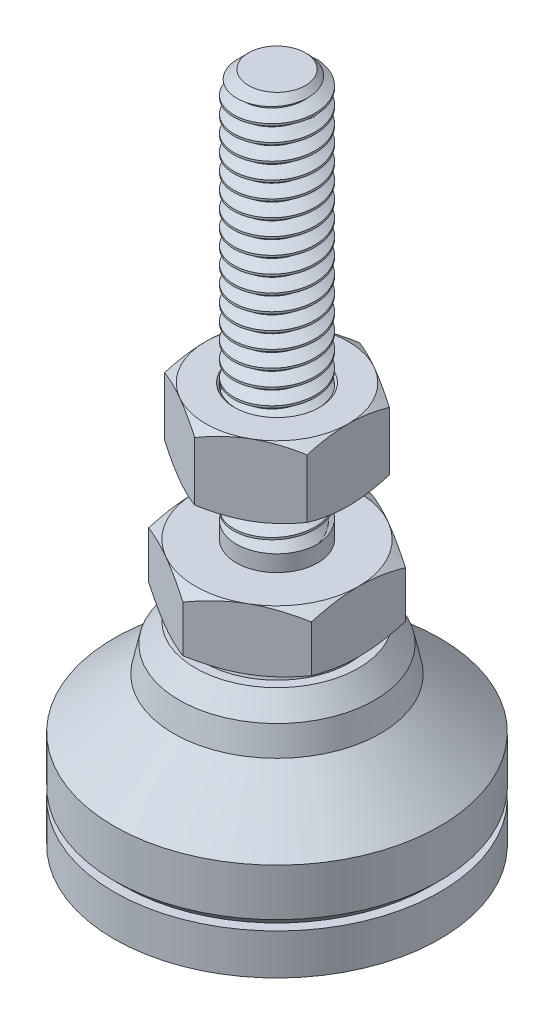
SolidWorks part; units mm, degrees
ref_plane "Front Plane" through (0, 0, 0) normal (0, 0, 1) x (1, 0, 0)
ref_plane "Top Plane" through (0, 0, 0) normal (0, 1, 0) x (1, 0, 0)
ref_plane "Right Plane" through (0, 0, 0) normal (1, 0, 0) x (0, 0, -1)
sketch "Sketch1" plane through (0, 0, 0) normal (0, 0, 1) x (1, 0, 0)
  line L0 (0, 0) -> (0, 52.3875) construction
  line L1 (-12.7, 0) -> (12.7, 0) construction
  line L2 (-3.175, 52.3875) -> (3.175, 52.3875) construction
  line L3 (-6.35, 15.875) -> (6.35, 15.875) construction
  point P7 (0, 20.6375)
  point P10 (0, 15.875)
  point P11 (-6.35, 20.6375)
  point P12 (0, 3.175)
  dimension "D1" = 3.175
sketch "Sketch2" plane through (0, 0, 0) normal (0, 0, 1) x (1, 0, 0)
  line L0 (0, 3.175) -> (0, 7.747)
  line L1 (-5.842, 15.875) -> (-6.35, 15.875) construction
  line L2 (-7.62, 13.589) -> (-6.35, 15.113)
  line L3 (-6.35, 15.113) -> (-5.6397, 15.113)
  line L4 (-7.62, 13.589) -> (-8.0645, 11.557)
  line L5 (-8.0645, 11.557) -> (-12.7, 7.62)
  line L6 (-12.7, 7.62) -> (-12.7, 3.937)
  line L7 (-11.938, 3.175) -> (0, 3.175)
  line L8 (-7.62, 13.589) -> (0, 13.589) construction
  line L9 (-5.842, 13.589) -> (-5.842, 15.875) construction
  line L10 (-12.7, 3.937) -> (-11.938, 3.175)
  line L11 (-11.938, 3.175) -> (-12.7, 3.175) construction
  line L12 (-12.7, 3.175) -> (-12.7, 3.937) construction
  line L13 (0, 15.875) -> (0, 52.3875) construction
  line L14 (-3.175, 52.3875) -> (3.175, 52.3875) construction
  line L15 (-6.35, 15.875) -> (6.35, 15.875) construction
  circle A0 centre (0, 13.589) radius 5.842 construction
  arc A2 (-5.6397, 15.113) -> (0, 7.747) centre (0, 13.589) ccw
  dimension "D1" = 16.129
  dimension "D2" = 15.24
  dimension "D3" = 12.7
  dimension "D4" = 0.508
  dimension "H3" = 2.032
  dimension "C1" = 0.762
  dimension "H4" = 1.524
  dimension "H2" = 3.937
  dimension "H1" = 4.445
revolve "Revolve1" add sketch "Sketch2" angle 360 about L0
sketch "Sketch12" plane through (0, 0, 0) normal (0, 0, 1) x (1, 0, 0)
  line L0 (0, 15.875) -> (-5.3762, 15.875)
  line L1 (0, 15.875) -> (0, 7.747)
  arc A0 (-5.3762, 15.875) -> (0, 7.747) centre (0, 13.589) ccw
  circle A1 centre (0, 13.589) radius 5.842 construction
revolve "Revolve2" add sketch "Sketch12" angle 360 about L1
sketch "Sketch4" plane through (0, 15.875, 0) normal (0, 1, 0) x (1, 0, 0)
  line L1 (0, 7.3323) -> (-6.35, 3.6662)
  line L2 (-6.35, 3.6662) -> (-6.35, -3.6662)
  line L3 (-6.35, -3.6662) -> (0, -7.3323)
  line L4 (0, -7.3323) -> (6.35, -3.6662)
  line L5 (6.35, -3.6662) -> (6.35, 3.6662)
  line L6 (6.35, 3.6662) -> (0, 7.3323)
  circle A0 centre (0, 0) radius 6.35 construction
extrude "Boss-Extrude1" add sketch "Sketch4" along normal up to vertex (4.7625 mm away) up to point (0, 20.6375, 0)
sketch "Sketch5" plane through (0, 0, 0) normal (1, 0, 0) x (0, 0, -1)
  line L0 (-8.3147, 20.6375) -> (-8.3147, 15.875)
  line L1 (-8.3147, 15.875) -> (-6.35, 15.875)
  line L2 (-6.35, 15.875) -> (-7.3323, 16.4422)
  line L3 (-7.3323, 16.4422) -> (-7.3323, 20.0703)
  line L4 (-7.3323, 20.0703) -> (-6.35, 20.6375)
  line L5 (-6.35, 20.6375) -> (-8.3147, 20.6375)
  line L9 (-7.3323, 20.6375) -> (-7.3323, 15.875) construction
  dimension "D1" = 30
revolve "Cut-Revolve2" cut sketch "Sketch5" angle 360 about L0
sketch "Sketch6" plane through (0, 20.6375, 0) normal (0, 1, 0) x (1, 0, 0)
  circle A0 centre (0, 0) radius 3.175
extrude "Boss-Extrude2" add sketch "Sketch6" along normal up to vertex (31.75 mm away) separate body up to point (0, 52.3875, 0)
sketch "Sketch7" plane through (0, 52.3875, 0) normal (0, 1, 0) x (1, 0, 0)
  circle A1 centre (0, 0) radius 3.175
  circle A2 centre (0, 0) radius 3.175
  point P0 (3.175, 0)
  dimension "D1" = 0
curve "Helix/Spiral1" pitch 1.27 height 33.02 turns 26 parameters "Pitch"=1.27
sketch "Sketch8" plane through (0, 0, 0) normal (0, 0, 1) x (1, 0, 0)
  line L0 (3.3125, 53.5781) -> (3.3125, 52.3081) construction
  line L1 (3.3125, 52.3081) -> (2.2126, 52.9431) construction
  line L2 (2.2126, 52.9431) -> (3.3125, 53.5781) construction
  line L3 (2.3501, 53.0225) -> (2.3501, 52.8638) construction
  line L4 (3.175, 53.4988) -> (3.175, 52.3875) construction
  line L5 (2.2126, 52.9431) -> (2.3501, 52.9431) construction
  line L6 (3.175, 52.9431) -> (3.3125, 52.9431) construction
  line L7 (3.2437, 53.5384) -> (2.3501, 53.0225)
  line L8 (2.3501, 53.0225) -> (2.3501, 52.8638)
  line L9 (2.3501, 52.8638) -> (3.2437, 52.3478)
  line L10 (3.2437, 52.3478) -> (3.2437, 53.5384)
  line L11 (3.3125, 52.3081) -> (3.175, 52.3081) construction
  line L12 (3.175, 52.3081) -> (3.175, 36.4331) construction
  line L20 (3.175, 20.6375) -> (3.175, 52.3875) construction
  point P11 (3.2437, 52.9431)
  dimension "D1" = 1.27
  dimension "D2" = 0.1588
  dimension "D3" = 15.875
sketch "Sketch9" plane through (0, 52.3875, 0) normal (0, 1, 0) x (1, 0, 0)
  circle A0 centre (0, 0) radius 2.2126
sweep "Cut-Sweep1" cut profiles "Sketch8" path "Helix/Spiral1" align with end faces yes
extrude "Cut-Extrude1" cut sketch "Sketch9" against normal up to vertex (31.75 mm away) draft 45 flip side to cut up to point (0, 20.6375, 0)
combine bodies "Combine1" operation type add bodies to combine 107 104
ref_plane "Plane1" through (0, 31.2208, 0) normal (0, 1, 0) x (-1, 0, 0)
sketch "Sketch10" plane through (0, 31.2208, 0) normal (0, 1, 0) x (-1, 0, 0)
  line L1 (0, 6.4158) -> (-5.5563, 3.2079)
  line L2 (-5.5563, 3.2079) -> (-5.5562, -3.2079)
  line L3 (-5.5562, -3.2079) -> (0, -6.4158)
  line L4 (0, -6.4158) -> (5.5562, -3.2079)
  line L5 (5.5562, -3.2079) -> (5.5562, 3.2079)
  line L6 (5.5562, 3.2079) -> (0, 6.4158)
  circle A0 centre (0, 0) radius 5.5562 construction
  circle A1 centre (0, 0) radius 3.175
  dimension "Nut Width" = 11.1125
extrude "Boss-Extrude3" add sketch "Sketch10" against normal blind 5.5562 separate body
sketch "Sketch11" plane through (0, 0, 0) normal (1, 0, 0) x (0, 0, -1)
  line L0 (-7.2754, 25.6646) -> (-7.2754, 31.2208)
  line L1 (-7.2754, 31.2208) -> (-5.5562, 31.2208)
  line L2 (-5.5562, 31.2208) -> (-6.4158, 30.7246)
  line L3 (-6.4158, 30.7246) -> (-6.4158, 26.1608)
  line L4 (-6.4158, 26.1608) -> (-5.5562, 25.6646)
  line L5 (-5.5562, 25.6646) -> (-7.2754, 25.6646)
  line L6 (-6.4158, 25.6646) -> (-6.4158, 31.2208) construction
  line L11 (0, 25.6646) -> (0, 31.2208)
  line L12 (0, 31.2208) -> (3.3338, 31.2208)
  line L13 (3.3338, 31.2208) -> (3.175, 31.0621)
  line L14 (3.175, 31.0621) -> (3.175, 25.8233)
  line L15 (3.175, 25.8233) -> (3.3338, 25.6646)
  line L16 (3.3338, 25.6646) -> (0, 25.6646)
  line L17 (3.175, 25.6646) -> (3.175, 31.2208) construction
  line L19 (0, 0) -> (0, 52.3875) construction
  dimension "D2" = 45
  dimension "D3" = 0.1588
  dimension "D1" = 60
revolve "Cut-Revolve3" cut sketch "Sketch11" angle 360 about L0
sketch "Sketch13" plane through (0, 0, 0) normal (0, 0, 1) x (1, 0, 0)
  line L0 (0, 0) -> (0, 52.3875) construction
  line L1 (0, 25.0825) -> (3.175, 21.9075)
  line L2 (0, 25.0825) -> (0, 20.6375)
  line L3 (0, 20.6375) -> (3.175, 20.6375)
  line L4 (3.175, 21.9075) -> (3.175, 20.6375)
  dimension "D1" = 45
  dimension "D2" = 1.27
revolve "Revolve3" add sketch "Sketch13" angle 360 about L2
sketch "SketchX" plane through (0, 0, 0) normal (0, 0, 1) x (1, 0, 0)
  line L0 (0, 13.589) -> (-5.0642, 52.0556)
  line L1 (0, 13.589) -> (5.0642, 52.0556)
  line L2 (0, 0) -> (0, 52.3875) construction
  line L3 (0, 13.589) -> (0, 52.3875)
  arc A0 (-5.0642, 52.0556) -> (5.0642, 52.0556) centre (0, 13.589) cw construction
  dimension "D1" = 7.5
sketch "Sketch14" plane through (0, 0, 0) normal (0, 0, 1) x (1, 0, 0)
  line L1 (0, 0) -> (12.7, 0)
  line L2 (0, 0) -> (0, 3.175)
  line L3 (0, 3.175) -> (12.7, 3.175)
  line L4 (12.7, 0) -> (12.7, 3.175)
  point P5 (12.7, 1.5875)
revolve "Revolve4" add sketch "Sketch14" angle 360 about L2
equation "\"D3@Helix/Spiral1\" = \"Pitch@Helix/Spiral1\" + \"Thread Lg.@Sketch1\""
equation "\"D1@Sketch8\" = \"Pitch@Helix/Spiral1\" "
equation "\"D2@Sketch8\" = \"D1@Sketch8\" / 8"
equation "\"D1@Plane1\" = \"Thread Lg.@Sketch1\" / 1.5"
equation "\"D3@Sketch11\" = \"Pitch@Helix/Spiral1\" / 8"
equation "\"D2@Sketch13\" = \"Pitch@Helix/Spiral1\""
equation "\"D3@Sketch8\" = \"Thread Lg.@Sketch1\" / 2"
